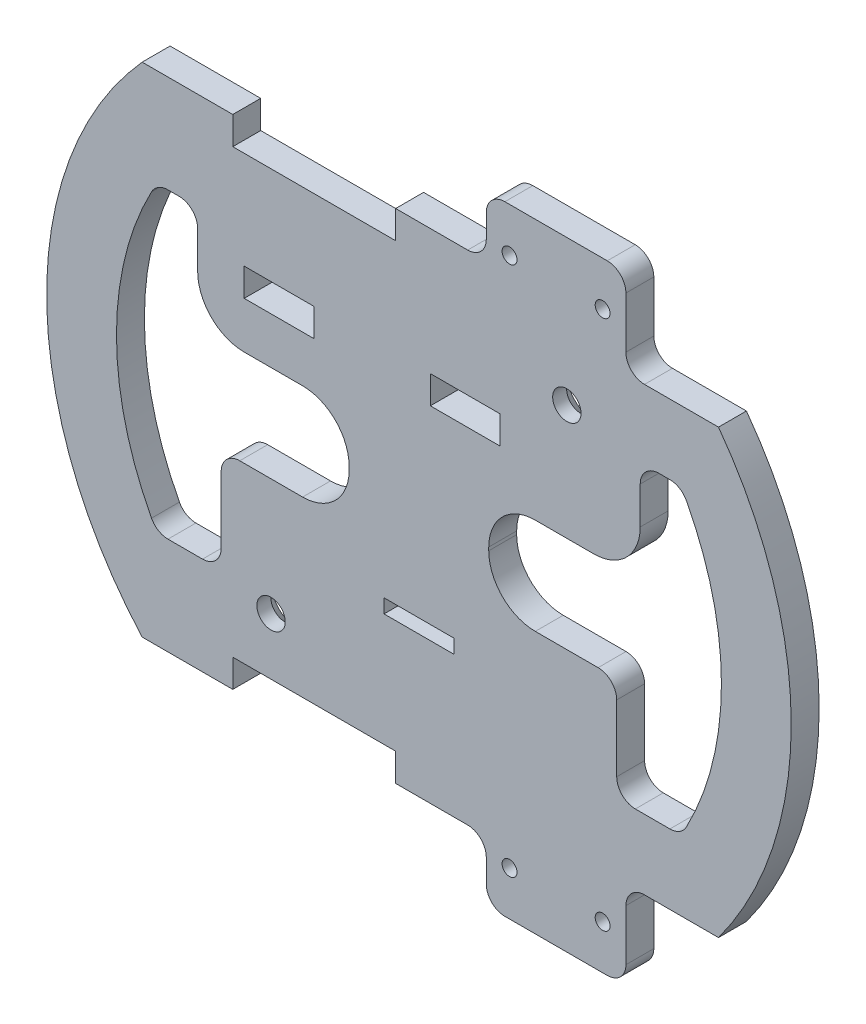
SolidWorks part; units mm, degrees
ref_plane "Plano frontal" through (0, 0, 0) normal (0, 0, 1) x (1, 0, 0)
ref_plane "Plano superior" through (0, 0, 0) normal (0, 1, 0) x (1, 0, 0)
ref_plane "Plano direito" through (0, 0, 0) normal (1, 0, 0) x (0, 0, -1)
sketch "Esboço1" plane through (0, 0, 0) normal (0, 0, 1) x (1, 0, 0)
  line L0 (80, 0) -> (0, 0) construction
  line L1 (-80, -66.5) -> (80, -66.5)
  line L2 (-80, -66.5) -> (-80, 66.5)
  line L3 (-80, 66.5) -> (80, 66.5)
  line L4 (80, -66.5) -> (80, 66.5)
  line L5 (-80, -66.5) -> (80, 66.5) construction
  line L6 (-80, 66.5) -> (80, -66.5) construction
  line L7 (80, 47.5) -> (-80, 47.5) construction
  line L8 (80, -47.5) -> (-80, -47.5) construction
  line L9 (14.4719, 66.5) -> (14.4719, 53.5)
  line L10 (0, 0) -> (0, 66.5) construction
  line L11 (44.4719, 47.5) -> (44.4719, 66.5)
  line L12 (44.4719, -47.5) -> (44.4719, -66.5)
  line L13 (14.4719, -66.5) -> (14.4719, -53.5)
  line L14 (14.4719, 53.5) -> (-59.479, 53.5)
  line L15 (14.4719, -53.5) -> (-59.479, -53.5)
  line L16 (-5.0035, 47.5) -> (-40.0035, 47.5)
  line L17 (-5.0035, 47.5) -> (-5.0035, 53.5)
  line L18 (-31.7837, -35.2994) -> (31.7837, 35.2994) construction
  line L19 (-42.5, -20.2) -> (-42.5, -14.2) construction
  line L20 (-7.5, -20.2) -> (7.5, -20.2)
  line L21 (-7.5, -20.2) -> (-7.5, -23.2)
  line L22 (-7.5, -23.2) -> (7.5, -23.2)
  line L23 (7.5, -20.2) -> (7.5, -23.2)
  line L24 (-7.5, -20.2) -> (7.5, -23.2) construction
  line L25 (-7.5, -23.2) -> (7.5, -20.2) construction
  line L26 (-37.55, 26.5) -> (-22.55, 26.5)
  line L27 (-37.55, 26.5) -> (-37.55, 20.5)
  line L28 (-37.55, 20.5) -> (-22.55, 20.5)
  line L29 (-22.55, 26.5) -> (-22.55, 20.5)
  line L30 (-37.55, 26.5) -> (-22.55, 20.5) construction
  line L31 (-37.55, 20.5) -> (-22.55, 26.5) construction
  line L32 (17.45, 20.5) -> (2.45, 20.5)
  line L33 (17.45, 20.5) -> (17.45, 26.5)
  line L34 (17.45, 26.5) -> (2.45, 26.5)
  line L35 (2.45, 20.5) -> (2.45, 26.5)
  line L36 (17.45, 20.5) -> (2.45, 26.5) construction
  line L37 (17.45, 26.5) -> (2.45, 20.5) construction
  line L38 (-42.5, -14.2) -> (42.5, -14.2) construction
  line L39 (42.5, -14.2) -> (42.5, -20.2) construction
  line L40 (42.5, -20.2) -> (-42.5, -20.2) construction
  line L41 (-56.2917, 32.5) -> (-47.55, 32.5)
  line L42 (-47.55, 32.5) -> (-47.55, 10.5)
  line L43 (-47.55, 10.5) -> (-15, 10.5)
  line L44 (-15, 10.5) -> (-15, -10.2)
  line L47 (-42.5, -32.5) -> (-56.2917, -32.5)
  line L48 (-42.5, -32.5) -> (-42.5, -10.2)
  line L49 (-42.5, -10.2) -> (-15, -10.2)
  line L50 (15, -10.2) -> (15, 10.5)
  line L51 (15, 10.5) -> (47.55, 10.5)
  line L52 (47.55, 10.5) -> (47.55, 32.5)
  line L53 (47.55, 32.5) -> (56.2917, 32.5)
  line L54 (56.2917, -32.5) -> (42.5, -32.5)
  line L55 (15, -10.2) -> (42.5, -10.2)
  line L56 (42.5, -10.2) -> (42.5, -32.5)
  line L57 (15, 10.5) -> (-15, 10.5) construction
  line L58 (-21.0674, -35.2994) -> (-42.5, -35.2994) construction
  line L59 (-5.0035, 53.5) -> (-40.0035, 53.5)
  line L60 (-40.0035, 47.5) -> (-40.0035, 53.5)
  line L61 (-5.0035, 47.5) -> (-40.0035, 53.5) construction
  line L62 (-5.0035, 53.5) -> (-40.0035, 47.5) construction
  line L63 (-5.0035, -53.5) -> (-40.0035, -53.5)
  line L64 (-40.0035, -47.5) -> (-40.0035, -53.5)
  line L65 (-5.0035, -47.5) -> (-40.0035, -47.5)
  line L66 (-5.0035, -47.5) -> (-5.0035, -53.5)
  line L67 (24.9009, 47.5) -> (24.9009, 66.5) construction
  line L69 (44.4719, 47.5) -> (64.372, 47.5)
  line L70 (44.4719, -47.5) -> (64.372, -47.5)
  circle A0 centre (0, 0) radius 80
  circle A1 centre (-31.7837, -35.2994) radius 3.05
  circle A2 centre (31.7837, 35.2994) radius 3.05
  circle A3 centre (19.4719, 57) radius 1.6
  circle A8 centre (19.4719, -57) radius 1.6
  arc A9 (-56.2917, -32.5) -> (-56.2917, 32.5) centre (0, 0) cw
  arc A10 (56.2917, -32.5) -> (56.2917, 32.5) centre (0, 0) ccw
  circle A11 centre (39.4719, 57) radius 1.6
  circle A12 centre (39.4719, -57) radius 1.6
  point P0 (0, 0)
  point P17 (-22.5035, 50.5)
  point P22 (44.4719, 66.5)
  point P34 (-30.05, 23.5)
  point P44 (0, -21.7)
  point P53 (9.95, 23.5)
  point P58 (0, -20.2)
  point P65 (-65, 0)
  point P80 (0, 10.5)
  point P83 (24.9009, 57)
  point P84 (-22.5035, 53.5)
  dimension "D6" = 6.1
  dimension "D7" = 6
  dimension "D18" = 15
  dimension "D25" = 3.2
  dimension "D1" = 95
  dimension "D2" = 19
  dimension "D3" = 160
  dimension "D4" = 95
  dimension "D5" = 48
  dimension "D8" = 5
  dimension "D9" = 3
  dimension "D10" = 6
  dimension "D11" = 15
  dimension "D12" = 20.2
  dimension "D13" = 40.7
  dimension "D14" = 25
  dimension "D15" = 2.45
  dimension "D16" = 85
  dimension "D17" = 35
  dimension "D19" = 10
  dimension "D20" = 10
  dimension "D21" = 10
  dimension "D22" = 30
  dimension "D23" = 30
  dimension "D24" = 5
  dimension "D26" = 15
extrude "Ressalto-extrusão1" add sketch "Esboço1" along normal blind 6 contours A0 L13 L1 L3 L9 A10 L54 L56 L55 L50 L51 L52 L53 L32 L35 L34 L33 L26 L29 L28 L27 L20 L23 L22 L21 A1 A2 A3 A11 region at (1.8253, 0.1118, 0)
chamfer "Chanfro1" distance 3 angle 45 2 edges at (34.8337, 35.2994, 0) (-28.7337, -35.2994, 0)
fillet "Filete1" radius 4 18 edges at (56.2917, 32.5, 3) (47.55, 32.5, 3) (42.5, -32.5, 3) (56.2917, -32.5, 3) (-42.5, -32.5, 3) (-56.2917, -32.5, 3) (42.5, -10.2, 3) (-42.5, -10.2, 3) (-47.55, 32.5, 3) (-56.2917, 32.5, 3) (14.4719, -53.5, 3) (14.4719, 53.5, 3) (44.4719, 47.5, 3) (44.4719, -47.5, 3) (14.4719, 66.5, 3) (44.4719, 66.5, 3) (44.4719, -66.5, 3) (14.4719, -66.5, 3)
fillet "Filete2" radius 10 6 edges at (15, -10.2, 3) (-15, -10.2, 3) (-15, 10.5, 3) (15, 10.5, 3) (47.55, 10.5, 3) (-47.55, 10.5, 3)
